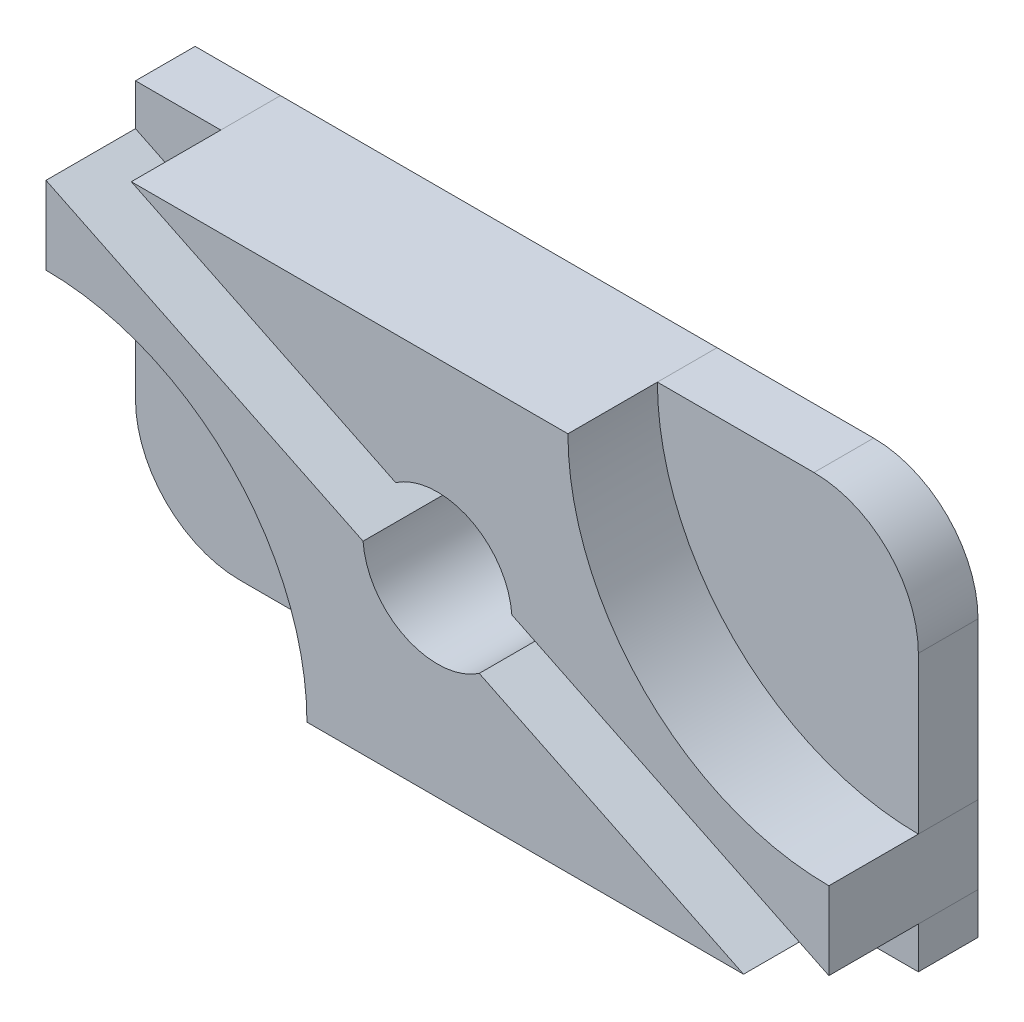
SolidWorks part; units mm, degrees
ref_plane "Front Plane" through (0, 0, 0) normal (0, 0, 1) x (1, 0, 0)
ref_plane "Top Plane" through (0, 0, 0) normal (0, 1, 0) x (1, 0, 0)
ref_plane "Right Plane" through (0, 0, 0) normal (1, 0, 0) x (0, 0, -1)
sketch "Sketch1" plane through (0, 0, 0) normal (0, 0, 1) x (1, 0, 0)
  line L0 (-41.0558, 25.5) -> (-5.6054, 8.2812)
  line L1 (-38.5, -25.5) -> (52.5, -25.5)
  line L2 (-52.5, -11.5) -> (-52.5, 25.5)
  line L3 (-52.5, 25.5) -> (38.5, 25.5)
  line L4 (52.5, -25.5) -> (52.5, 11.5)
  line L5 (-52.5, -25.5) -> (52.5, 25.5) construction
  line L6 (-52.5, 25.5) -> (52.5, -25.5) construction
  line L7 (41.0558, -25.5) -> (5.6054, -8.2812)
  line L8 (-9.9745, -0.7138) -> (-52.5, 19.9414)
  line L9 (9.9745, 0.7138) -> (52.5, -19.9414)
  circle A0 centre (0, 0) radius 10
  arc A1 (17.5, 25.5) -> (52.5, -9.5) centre (52.5, 25.5) ccw
  arc A2 (-17.5, -25.5) -> (-52.5, 9.5) centre (-52.5, -25.5) ccw
  arc A3 (38.5, 25.5) -> (52.5, 11.5) centre (38.5, 11.5) cw
  arc A4 (-38.5, -25.5) -> (-52.5, -11.5) centre (-38.5, -11.5) cw
  point P0 (0, 0)
  dimension "D3" = 70
  dimension "D4" = 70
  dimension "D5" = 20
  dimension "D7" = 14
  dimension "D1" = 105
  dimension "D2" = 51
  dimension "D6" = 10
extrude "Boss-Extrude1" add sketch "Sketch1" along normal blind 20 contours A2 L1 L7 A0 L8 L2 | A1 L3 L0 A0 L9 L4 region at (8.0747, 10.3209, 0) region at (-8.0747, -10.3209, 0)
extrude "Boss-Extrude2" add sketch "Sketch1<3>" along normal blind 8 contours A3 L3 A1 L4 | A4 L1 A2 L2 | A0 L0 L3 L2 L8 | A0 L7 L1 L4 L9 region at (-29.2672, 14.0558, 0) region at (37.1094, 10.1094, 0) region at (29.2672, -14.0558, 0) region at (-37.1094, -10.1094, 0)
sketch "Sketch1<3>" plane through (0, 0, 0) normal (0, 0, 1) x (1, 0, 0) same geometry as "Sketch1"
